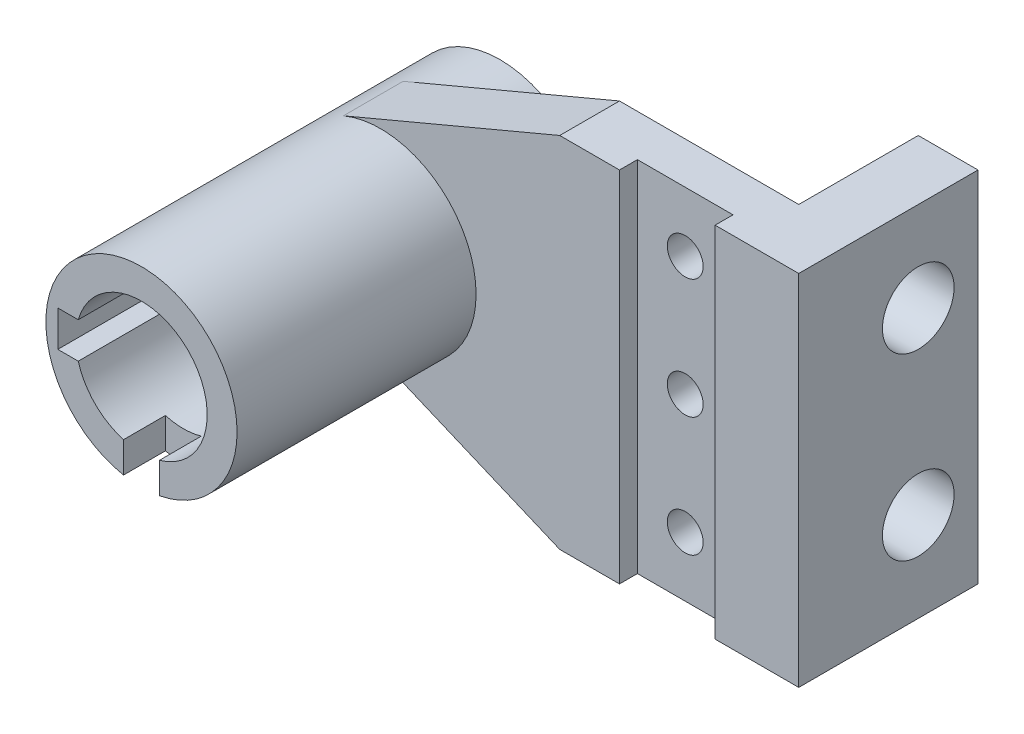
SolidWorks part; units mm, degrees
ref_plane "Front Plane" through (0, 0, 0) normal (1, 0, 0) x (0, 1, 0)
ref_plane "Top Plane" through (0, 0, 0) normal (0, 0, 1) x (0, 1, 0)
ref_plane "Right Plane" through (0, 0, 0) normal (0, 1, 0) x (-1, 0, 0)
sketch "Sketch2" plane through (0, 0, 0) normal (0, 0, 1) x (0, 1, 0)
  line L0 (-14.745, 6.2117) -> (-30, -30)
  line L1 (-30, -30) -> (-30, -70)
  line L2 (-30, -70) -> (0, -70)
  line L3 (0, -70) -> (0, 0)
  line L4 (-30, -40) -> (0, -40)
  line L5 (-30, -56) -> (0, -56)
  line L6 (0, 0) -> (0, 14)
  line L7 (0, 14) -> (-3, 14)
  line L8 (-3, 14) -> (-3, 10.583)
  line L9 (0, 14) -> (0, 16)
  circle A0 centre (0, 0) radius 16
  circle A1 centre (0, 0) radius 11
  circle A2 centre (0, -48) radius 3
  circle A3 centre (-20, -48) radius 3
  point P16 (0, -11)
  dimension "D3" = 32
  dimension "D4" = 22
  dimension "D6" = 6
  dimension "D1" = 40
  dimension "D2" = 10
  dimension "D5" = 20
  dimension "D7" = 30
  dimension "D8" = 70
  dimension "D9" = 8
  dimension "D10" = 14
  dimension "D11" = 3
  dimension "D12" = 25
extrude "Boss-Extrude1" add sketch "Sketch2" against normal blind 10 contours A0 L0 L1 L4 L3 | L5 L1 L2 L3 | A2 L3 L4 L1 L5 A3 region at (25.527, -14.519, 0) region at (48, -15.1204, 0) region at (63, -15, 0)
extrude "Cut-Extrude1" cut sketch "Sketch2<5>" against normal blind 3 contours A2 L3 L4 L1 L5 A3 region at (48, -15.1204, 0)
sketch "Sketch2<5>" plane through (0, 0, 0) normal (0, 0, 1) x (0, 1, 0) same geometry as "Sketch2"
extrude "Boss-Extrude2" add sketch "Sketch2<6>" along normal blind 40 and the other way blind 20 contours A1 L8 L7 L9 A0 L3 region at (-13.0321, -8.6512, 0)
sketch "Sketch2<6>" plane through (0, 0, 0) normal (0, 0, 1) x (0, 1, 0) same geometry as "Sketch2"
sketch "Sketch3" plane through (70, 0, 0) normal (1, 0, 0) x (0, 1, 0)
  line L0 (-30, -10) -> (-30, -30)
  line L1 (-30, -30) -> (0, -30)
  line L2 (0, -30) -> (0, -10)
  line L3 (-30, 0) -> (0, 0) construction
  circle A0 centre (-15, -20) radius 6
  line M5 (-30, -10) -> (0, -10)
  dimension "D4" = 12
  dimension "D1" = 10
  dimension "D2" = 30
  dimension "D3" = 15
extrude "Boss-Extrude3" add sketch "Sketch3" against normal blind 10 contours L1 L2 L0 A0 M5 region at (70, -15, -10.3606)
mirror "Mirror1" about plane through (0, 0, -10) normal (0, 1, 0) of bodies 105
sketch "Sketch4" plane through (0, 0, 40) normal (0, 0, 1) x (1, 0, 0)
  line L0 (0, 0) -> (0, -27.0465)
  line L1 (0, -27.0465) -> (-3, -27.0465)
  line L2 (-3, -27.0465) -> (-3, -4.9462)
  line L3 (-3, -4.9462) -> (3, -4.9462)
  line L4 (3, -4.9462) -> (3, -27.5231)
  line L5 (3, -27.5231) -> (0, -27.0465)
  arc M8 (-10.583, 3) -> (-10.583, -3) centre (0, 0) cw
  circle M11 centre (0, 0) radius 16
  dimension "D1" = 3
  dimension "D2" = 6
extrude "Cut-Extrude2" cut sketch "Sketch4" against normal blind 7 contours L4 L0 M8 M11 | L2 L0 M11 M8 region at (1.5065, -13.3831, 40) region at (-1.5065, -13.3831, 40)
